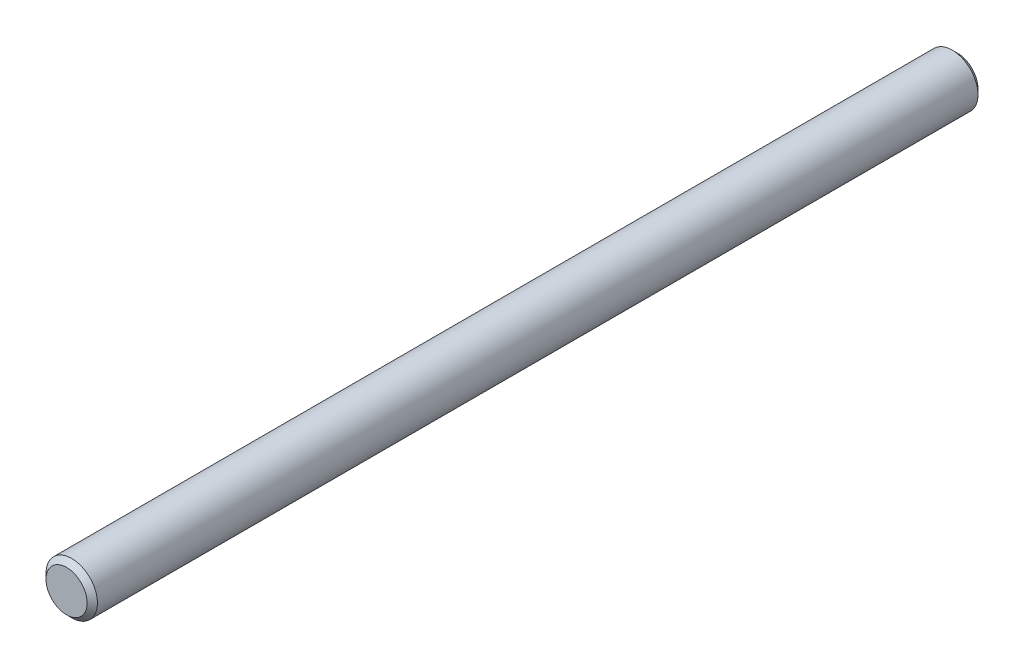
SolidWorks part; units mm, degrees
ref_plane "Front" through (0, 0, 0) normal (0, 0, 1) x (1, 0, 0)
ref_plane "Top" through (0, 0, 0) normal (0, 1, 0) x (1, 0, 0)
ref_plane "Right" through (0, 0, 0) normal (1, 0, 0) x (0, 0, -1)
sketch "Sketch1" plane through (0, 0, 0) normal (0, 0, 1) x (1, 0, 0)
  circle A0 centre (0, 0) radius 6.35
  dimension "dia" = 12.7
extrude "Extrude1" add sketch "Sketch1" along normal mid plane 220
sketch "Sketch2" plane through (0, 0, 0) normal (1, 0, 0) x (0, 0, -1)
  line L0 (110, 6.35) -> (88, 6.35) construction
  line L1 (110, 6.35) -> (-110, 6.35) construction
  line L2 (88, 6.35) -> (88, -6.35) construction
  line L3 (-110, -6.35) -> (110, -6.35) construction
  line L4 (100, 6.35) -> (100, -6.35) construction
  line L5 (-110, -6.35) -> (110, -6.35) construction
  point P0 (-110, 6.35)
  point P1 (110, 6.35)
  point P15 (100, 0)
  point P16 (88, 0)
  dimension "D1" = 22
  dimension "D2" = 12
chamfer "Chamfer1" distance 1.27 angle 45 2 edges at (6.35, 0, -110) (6.35, 0, 110)
equation "\"D1@Chamfer1\" = \"dia@Sketch1\" * .1"
